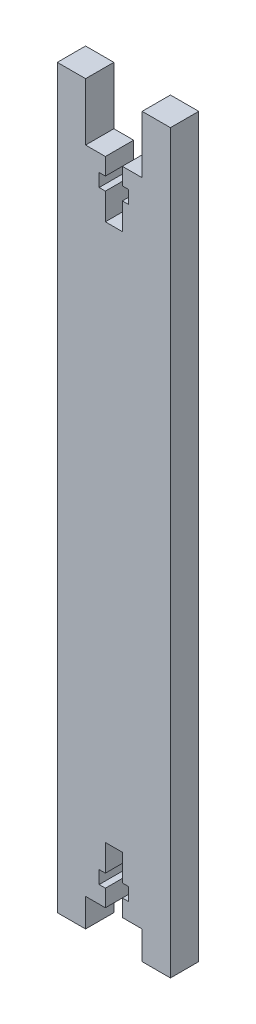
SolidWorks part; units mm, degrees
ref_plane "Front Plane" through (0, 0, 0) normal (0, 0, 1) x (1, 0, 0)
ref_plane "Top Plane" through (0, 0, 0) normal (0, 1, 0) x (1, 0, 0)
ref_plane "Right Plane" through (0, 0, 0) normal (1, 0, 0) x (0, 0, -1)
sketch "Sketch1" plane through (0, 0, 0) normal (0, 0, 1) x (1, 0, 0)
  line L0 (-1.5, 0) -> (-5, 0)
  line L1 (-5, -5) -> (-10, -5)
  line L2 (-10, -5) -> (-10, 0)
  line L3 (-5, -5) -> (-5, 0)
  line L4 (1.5, 0) -> (5, 0)
  line L5 (5, 0) -> (5, -5)
  line L6 (5, -5) -> (10, -5)
  line L7 (10, -5) -> (10, 0)
  line L8 (-1.5, 0) -> (1.5, 0) construction
  line L9 (1.5, 0) -> (1.5, 3)
  line L10 (1.5, 5.3) -> (2.6, 5.3)
  line L11 (-2.6, 3) -> (-2.6, 5.3)
  line L12 (2.6, 3) -> (1.5, 3)
  line L13 (1.5, 5.3) -> (1.5, 10)
  line L14 (1.5, 10) -> (-1.5, 10)
  line L15 (-1.5, 10) -> (-1.5, 5.3)
  line L16 (-1.5, 3) -> (-2.6, 3)
  line L17 (2.6, 5.3) -> (2.6, 3)
  line L18 (-2.6, 5.3) -> (-1.5, 5.3)
  line L19 (-1.5, 3) -> (-1.5, 0)
  line L20 (0, 10) -> (0, 0) construction
  line L21 (-10, 0) -> (-10, 115)
  line L23 (10, 115) -> (10, 0)
  line L24 (0, 105) -> (0, 115) construction
  line L25 (-1.5, 115) -> (1.5, 115) construction
  line L26 (-1.5, 112) -> (-1.5, 115)
  line L27 (-2.6, 109.7) -> (-1.5, 109.7)
  line L28 (2.6, 109.7) -> (2.6, 112)
  line L29 (-1.5, 112) -> (-2.6, 112)
  line L30 (-1.5, 105) -> (-1.5, 109.7)
  line L31 (1.5, 105) -> (-1.5, 105)
  line L32 (1.5, 109.7) -> (1.5, 105)
  line L33 (2.6, 112) -> (1.5, 112)
  line L34 (-2.6, 112) -> (-2.6, 109.7)
  line L35 (1.5, 109.7) -> (2.6, 109.7)
  line L36 (1.5, 115) -> (1.5, 112)
  line L37 (10, 120) -> (10, 115)
  line L39 (5, 115) -> (5, 120)
  line L40 (1.5, 115) -> (5, 115)
  line L41 (-5, 120) -> (-5, 115)
  line L42 (-10, 120) -> (-10, 115)
  line L44 (-1.5, 115) -> (-5, 115)
  line L45 (-10, 57.5) -> (10, 57.5) construction
  line L46 (-10, 120) -> (-10, 125.163)
  line L55 (-10, 125.163) -> (-5, 125.163)
  line L56 (-5, 125.163) -> (-5, 120)
  line L57 (5, 120) -> (5, 125.163)
  line L58 (5, 125.163) -> (10, 125.163)
  line L59 (10, 125.163) -> (10, 120)
  dimension "D1" = 5
  dimension "D2" = 5
  dimension "D3" = 5.2
  dimension "D4" = 3
  dimension "D5" = 2.3
  dimension "D6" = 3
  dimension "D7" = 10
  dimension "D8" = 62.5
  dimension "D14" = 10
extrude "Boss-Extrude1" add sketch "Sketch1" along normal blind 5
